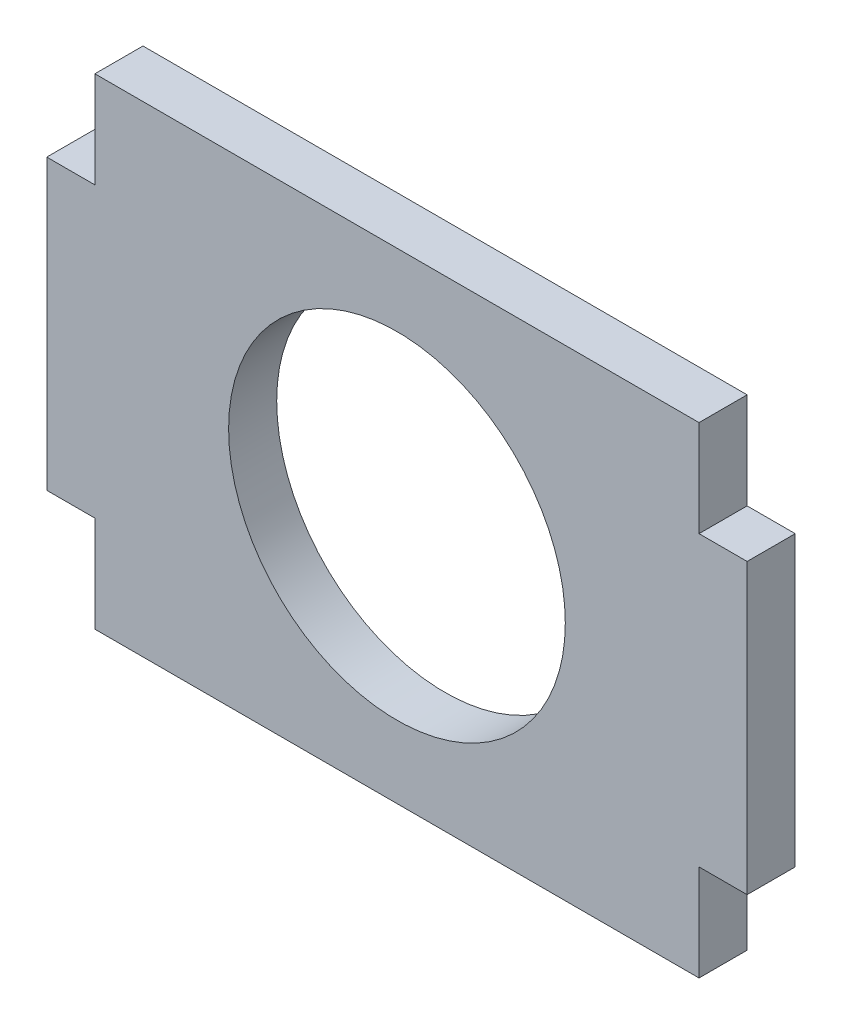
SolidWorks part; units mm, degrees
ref_plane "Front Plane" through (0, 0, 0) normal (0, 0, 1) x (1, 0, 0)
ref_plane "Top Plane" through (0, 0, 0) normal (0, 1, 0) x (1, 0, 0)
ref_plane "Right Plane" through (0, 0, 0) normal (1, 0, 0) x (0, 0, -1)
sketch "Sketch1" plane through (0, 0, 0) normal (0, 0, 1) x (1, 0, 0)
  line L0 (-23.114, -9.525) -> (-23.114, 9.525)
  line L1 (23.114, -9.525) -> (23.114, 9.525)
  line L2 (23.114, 9.525) -> (19.939, 9.525)
  line L3 (19.939, 9.525) -> (19.939, 15.875)
  line L4 (19.939, 15.875) -> (-19.939, 15.875)
  line L5 (-19.939, 15.875) -> (-19.939, 9.525)
  line L6 (-19.939, 9.525) -> (-23.114, 9.525)
  line L7 (-23.114, -9.525) -> (-19.939, -9.525)
  line L8 (-19.939, -9.525) -> (-19.939, -15.875)
  line L9 (-19.939, -15.875) -> (19.939, -15.875)
  line L10 (19.939, -15.875) -> (19.939, -9.525)
  line L11 (19.939, -9.525) -> (23.114, -9.525)
  line L12 (0, 0) -> (0, -15.875) construction
  line L13 (0, 0) -> (0, 15.875) construction
  circle A0 centre (0, 0) radius 11.1125
  point P3 (-19.939, -10.6681)
  point P6 (-23.114, 0)
  point P9 (23.114, 0)
  point P20 (-19.939, 7.6849)
  dimension "D1" = 22.225
  dimension "D2" = 39.878
  dimension "D3" = 3.175
  dimension "D4" = 6.35
  dimension "D5" = 31.75
extrude "Boss-Extrude1" add sketch "Sketch1" along normal blind 3.175
